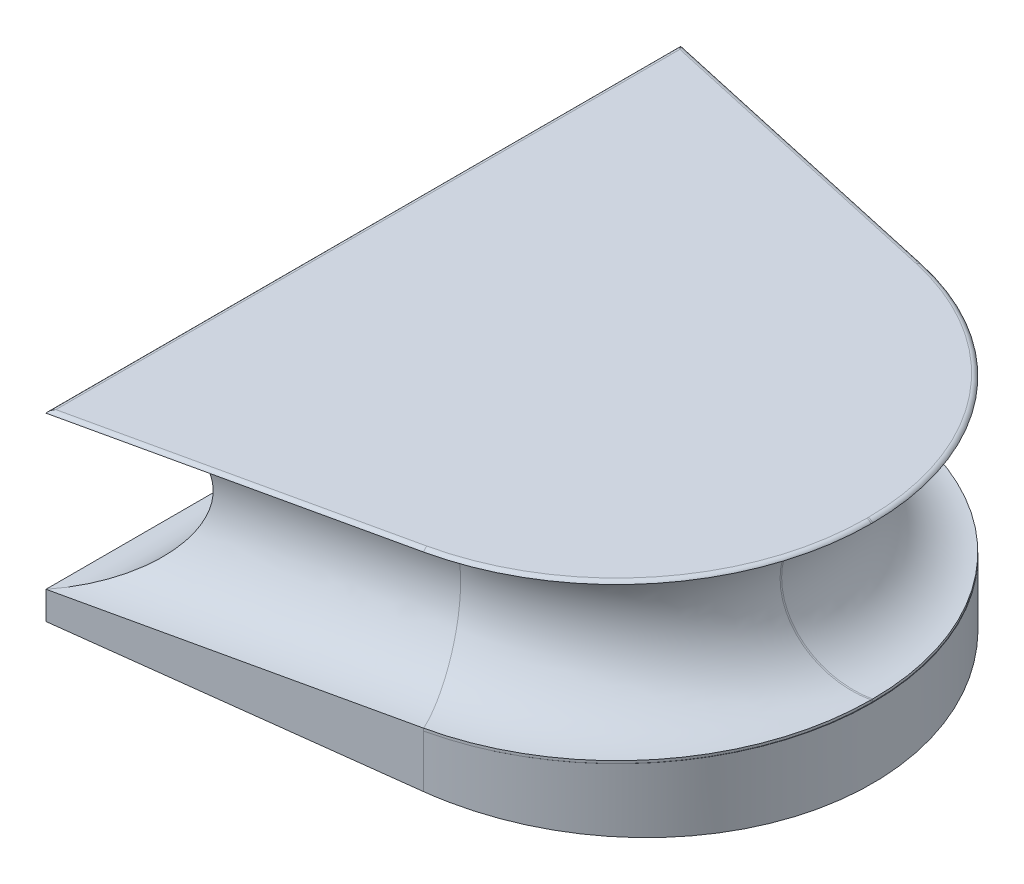
SolidWorks part; units mm, degrees
ref_plane "Front Plane" through (0, 0, 0) normal (0, 0, 1) x (1, 0, 0)
ref_plane "Top Plane" through (0, 0, 0) normal (0, 1, 0) x (1, 0, 0)
ref_plane "Right Plane" through (0, 0, 0) normal (1, 0, 0) x (0, 0, -1)
sketch "Sketch1" plane through (0, 0, 0) normal (0, 1, 0) x (1, 0, 0)
  line L4 (0, 0) -> (60.822, -13.4839)
  line L5 (100, -62.2987) -> (100, -62.6021)
  line L6 (60.822, -111.4169) -> (0, -124.9008)
  line L11 (0, 0) -> (0, -124.9008)
  arc A0 (60.822, -13.4839) -> (100, -62.2987) centre (50, -62.2987) cw
  arc A1 (100, -62.6021) -> (60.822, -111.4169) centre (50, -62.6021) cw
  dimension "D6" = 50
  dimension "D7" = 50
extrude "Extrude1" add sketch "Sketch1" along normal mid plane 31
sketch "Sketch2" plane through (0, 0, 0) normal (1, 0, 0) x (0, 0, -1)
  circle A0 centre (0, 0) radius 15
  dimension "D1" = 30
sweep "Cut-Sweep2" cut profiles "Sketch2" path "Sketch1<3>"
sketch "Sketch1<3>" plane through (0, 0, 0) normal (0, 1, 0) x (1, 0, 0) same geometry as "Sketch1"
sketch "Sketch6" plane through (0, -15.5, 0) normal (0, -1, 0) x (1, 0, 0)
  line L0 (0, 124.9008) -> (60.822, 111.4169)
  line L1 (0, 124.9008) -> (0, 0)
  line L2 (0, 0) -> (60.822, 13.4839)
  arc A0 (60.822, 111.4169) -> (60.822, 13.4839) centre (49.9664, 62.4504) cw
extrude "Extrude2" add sketch "Sketch6" along normal blind 75
sketch "Sketch7" plane through (0, 0, 0) normal (0, 0, 1) x (1, 0, 0)
  line L0 (0, -90.5) -> (0, -20.5)
  line L1 (0, -15) -> (0, -90.5) construction
  line L2 (0, -20.5) -> (100.1217, -29.2595)
  line L3 (100.1217, -90.5) -> (100.1217, -15.5) construction
  line L4 (100.1217, -29.2595) -> (100.1217, -90.5)
  line L5 (100.1217, -90.5) -> (0, -90.5)
  dimension "D1" = 85
  dimension "D2" = 70
extrude "Extrude3" cut sketch "Sketch7" along normal through all
fillet "Fillet1" radius 1 6 edges at (100, 15.5, 62.4504) (88.9942, 15.5, 93.8983) (30.411, 15.5, 118.1589) (0, 15.5, 62.4504) (30.411, 15.5, 6.742) (88.9942, 15.5, 31.0025)
